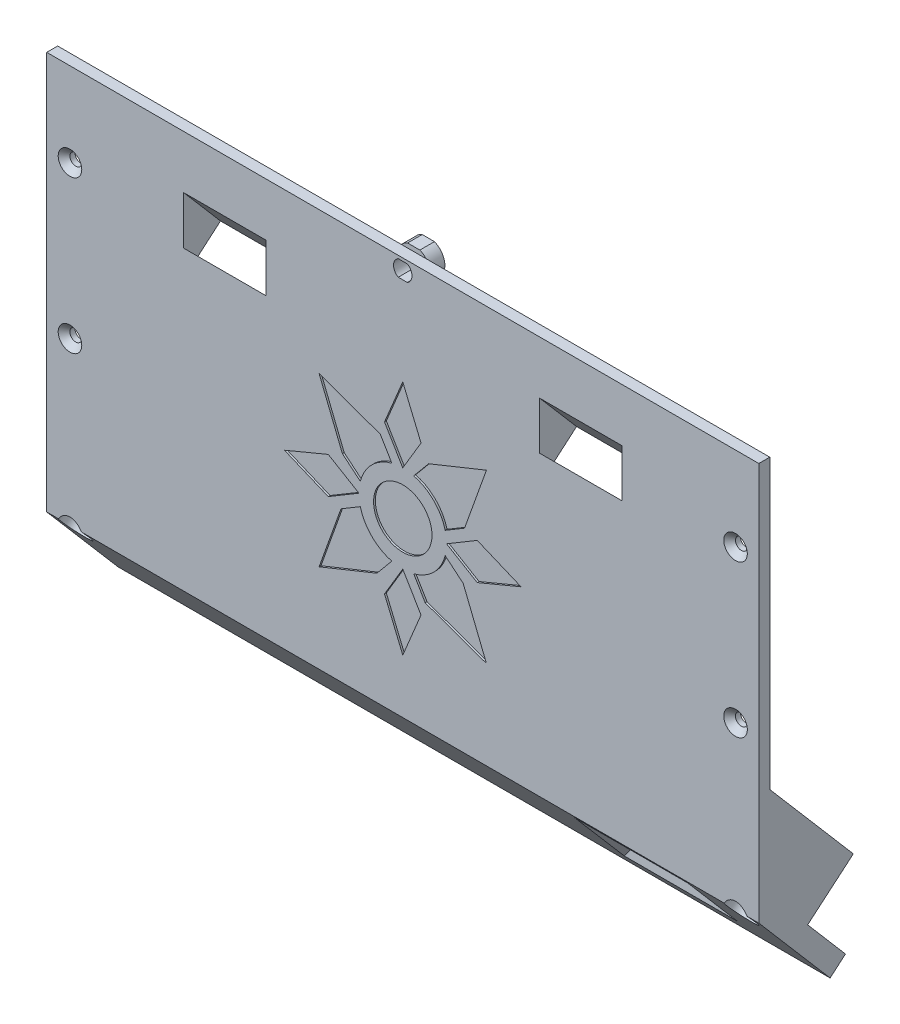
SolidWorks part; units mm, degrees
ref_plane "Alzado" through (0, 0, 0) normal (0, 0, 1) x (1, 0, 0)
ref_plane "Planta" through (0, 0, 0) normal (0, 1, 0) x (1, 0, 0)
ref_plane "Vista lateral" through (0, 0, 0) normal (1, 0, 0) x (0, 0, -1)
sketch "Croquis1" plane through (0, 0, 0) normal (0, 0, 1) x (1, 0, 0)
  line L0 (-97.5, 0) -> (97.5, 0)
  line L1 (97.5, 0) -> (97.5, 38)
  line L2 (97.5, 38) -> (-97.5, 38)
  line L3 (0, 0) -> (0, 28.0598) construction
  line L4 (-97.5, 0) -> (-97.5, 38)
  circle A2 centre (91.125, 15) radius 1.625
  circle A3 centre (-91.125, 15) radius 1.625
  point P13 (0, 38)
  point P14 (0, 0)
  dimension "D1" = 3.25
  dimension "D2" = 15
  dimension "D3" = 97.5
  dimension "D4" = 38
  dimension "D5" = 6.375
extrude "Saliente-Extruir1" add sketch "Croquis1" along normal blind 3
sketch "Croquis8" plane through (0, 0, 0) normal (0, -1, 0) x (1, 0, 0)
  line L1 (-97.5, 3) -> (97.5, 3)
  line L2 (-97.5, 3) -> (-97.5, 0)
  line L3 (-97.5, 0) -> (97.5, 0)
  line L4 (97.5, 3) -> (97.5, 0)
extrude "Saliente-Extruir5" add sketch "Croquis8" along normal blind 5
sketch "Croquis9" plane through (0, 38, 0) normal (0, 1, 0) x (1, 0, 0)
  line L1 (-97.5, 0) -> (97.5, 0)
  line L2 (-97.5, 0) -> (-97.5, -3)
  line L3 (-97.5, -3) -> (97.5, -3)
  line L4 (97.5, 0) -> (97.5, -3)
extrude "Saliente-Extruir6" add sketch "Croquis9" along normal blind 5
sketch "Croquis10" plane through (97.5, 0, 0) normal (1, 0, 0) x (0, 0, -1)
  line L0 (0, 35.3168) -> (11.1006, 22.3656)
  line L1 (1.23, 13.9055) -> (0, 12.8513)
  line L2 (0, 35.3168) -> (0, 12.8513)
  line L3 (0, -5) -> (0, 43) construction
  line L4 (11.1006, 22.3656) -> (1.23, 13.9055)
  line L6 (-3, 18.8408) -> (0, 15.3406) construction
  line L7 (-3, -5) -> (-3, 43) construction
  line L8 (-3, 18.8408) -> (5.5756, 26.191) construction
  dimension "D1" = 5
  dimension "D2" = 6.5
  dimension "D3" = 14.62
  dimension "D4" = 40.6
extrude "Saliente-Extruir7" add sketch "Croquis10" against normal blind 35 from offset 35 offset against normal yes
sketch "Croquis11" plane through (0, 7.4087, 6.35) normal (0, -0.7593, -0.6508) x (1, 0, 0)
  line L3 (60, -13.4833) -> (37.5, -13.4833)
  line L6 (37.5, -13.4833) -> (37.5, -21.9833)
  line L7 (37.5, -21.9833) -> (60, -21.9833)
  line L8 (60, -21.9833) -> (60, -13.4833)
  line L9 (62.5, -8.3633) -> (62.5, -22.9833) construction
  line L10 (27.5, -22.9833) -> (62.5, -22.9833) construction
  dimension "D1" = 8.5
  dimension "D2" = 22.5
  dimension "D3" = 2.5
  dimension "D4" = 1
extrude "Cortar-Extruir4" cut sketch "Croquis11" against normal through all both and the other way through all
sketch "Croquis12" plane through (62.5, 0, 0) normal (1, 0, 0) x (0, 0, -1)
  line L0 (11.1006, 22.3656) -> (0, 12.8513)
  line L1 (0, 12.8513) -> (0, 19.4365)
  line L2 (0, -5) -> (0, 43) construction
  line L3 (0, 19.4365) -> (7.8467, 26.162)
  line L4 (11.1006, 22.3656) -> (0, 35.3168) construction
  line L5 (7.8467, 26.162) -> (11.1006, 22.3656)
  dimension "D1" = 5
extrude "Cortar-Extruir5" cut sketch "Croquis12" against normal up to next
sketch "Croquis13" plane through (0, 11.205, 9.6039) normal (0, -0.7593, -0.6508) x (1, 0, 0)
  line L0 (27.5, -12.6488) -> (27.5, -22.9833) construction
  line L3 (27.5, -22.9833) -> (62.5, -22.9833) construction
  circle A0 centre (33.75, -17.8233) radius 1
  dimension "D1" = 2
  dimension "D3" = 5.16
  dimension "D2" = 6.25
extrude "Cortar-Extruir6" cut sketch "Croquis13" against normal blind 5
sketch "Croquis14" plane through (-97.5, 0, 0) normal (-1, 0, 0) x (0, 0, 1)
  line L0 (0, 19.4365) -> (-7.8467, 26.162)
  line L1 (-7.8467, 26.162) -> (0, 35.3168)
  line L2 (0, 35.3168) -> (0, 19.4365)
extrude "Saliente-Extruir8" add sketch "Croquis14" against normal blind 35 from offset 35 offset against normal yes
sketch "Croquis16" plane through (0, 11.205, 9.6039) normal (0, -0.7593, -0.6508) x (1, 0, 0)
  line L0 (0, 0) -> (0, -29.2293) construction
  line L5 (-37.5, -21.9833) -> (-60, -21.9833)
  line L6 (-60, -13.411) -> (-60, -21.9833)
  line L8 (-37.5, -13.411) -> (-60, -13.411)
  line L9 (60, -21.9833) -> (37.5, -21.9833) construction
  line L10 (-37.5, -13.411) -> (-37.5, -21.9833)
  line L11 (-62.5, -22.9833) -> (-62.5, -12.6488) construction
  dimension "D1" = 22.5
  dimension "D2" = 2.5
extrude "Cortar-Extruir7" cut sketch "Croquis16" against normal through all both and the other way through all
sketch "Croquis17" plane through (0, 11.205, 9.6039) normal (0, -0.7593, -0.6508) x (1, 0, 0)
  line L0 (0, 0) -> (0, -24) construction
  line L1 (-27.5, -22.9833) -> (-62.5, -22.9833) construction
  line L3 (-37.5, -21.9833) -> (-37.5, -13.411) construction
  circle A1 centre (-33.75, -17.8233) radius 1
  dimension "D1" = 5.16
  dimension "D2" = 3.75
extrude "Cortar-Extruir8" cut sketch "Croquis17" against normal blind 5
sketch "Croquis18" plane through (0, 0, 3) normal (0, 0, 1) x (1, 0, 0)
  line L0 (-97.5, 19) -> (97.5, 19) construction
  circle A2 centre (91.125, 23) radius 1.625
  circle A3 centre (-91.125, 23) radius 1.625
extrude "Cortar-Extruir9" cut sketch "Croquis18" against normal blind 10
sketch "Croquis19" plane through (0, 0, 3) normal (0, 0, 1) x (1, 0, 0)
  line L0 (-97.5, 43) -> (-97.5, -5) construction
  line L1 (-97.5, 19) -> (97.5, 19)
  line L2 (-97.5, 19) -> (-97.5, -5)
  line L3 (-97.5, -5) -> (97.5, -5)
  line L4 (97.5, 19) -> (97.5, -5)
extrude "Saliente-Extruir9" add sketch "Croquis19" against normal up to vertex (3 mm away) up to point (-97.5, -5, 0)
sketch "Croquis20" plane through (0, 0, 3) normal (0, 0, 1) x (1, 0, 0)
  line L0 (-97.5, 43) -> (97.5, 43) construction
  line L1 (-97.5, -5) -> (97.5, -5)
  line L2 (-97.5, -5) -> (-97.5, -33.69)
  line L3 (-97.5, -33.69) -> (97.5, -33.69)
  line L4 (97.5, -5) -> (97.5, -33.69)
  dimension "D1" = 76.69
extrude "Saliente-Extruir10" add sketch "Croquis20" against normal up to vertex (3 mm away) up to point (-97.5, -5, 0)
sketch "Croquis22" plane through (0, 0, 3) normal (0, 0, 1) x (1, 0, 0)
  line L0 (-97.5, 43) -> (-97.5, -33.69) construction
  line L1 (-97.5, 43) -> (97.5, 43)
  line L2 (-97.5, 43) -> (-97.5, 51.7993)
  line L3 (-97.5, 51.7993) -> (97.5, 51.7993)
  line L4 (97.5, 43) -> (97.5, 51.7993)
  line L5 (-97.5, 27.545) -> (-86.6825, 27.545)
  line L6 (-97.5, 27.545) -> (-97.5, 18.136)
  line L7 (-97.5, 18.136) -> (-86.6825, 18.136)
  line L8 (-86.6825, 27.545) -> (-86.6825, 18.136)
  line L9 (97.5, -33.69) -> (97.5, 43) construction
  line L10 (86.4429, 27.545) -> (97.5, 27.545)
  line L11 (86.4429, 27.545) -> (86.4429, 18.136)
  line L12 (86.4429, 18.136) -> (97.5, 18.136)
  line L13 (97.5, 27.545) -> (97.5, 18.136)
extrude "Saliente-Extruir11" add sketch "Croquis22" against normal up to vertex (3 mm away) up to point (-97.5, -33.69, 0)
sketch "Croquis23" plane through (0, 0, 3) normal (0, 0, 1) x (1, 0, 0)
  line L1 (-97.5, 51.7993) -> (-97.5, -33.69) construction
  line L2 (97.5, 51.7993) -> (-97.5, 51.7993) construction
  line L3 (0, -1.1555) -> (0, 35.7449) construction
  circle A0 centre (-91.125, 28.7993) radius 1.625
  circle A1 centre (-91.125, -12.8907) radius 1.625
  circle A2 centre (91.125, -12.8907) radius 1.625
  circle A3 centre (91.125, 28.7993) radius 1.625
  dimension "D1" = 6.375
  dimension "D2" = 23
  dimension "D3" = 41.69
  dimension "D4" = 3.25
extrude "Cortar-Extruir10" cut sketch "Croquis23" against normal blind 10
sketch "Croquis25" plane through (-97.5, 0, 0) normal (-1, 0, 0) x (0, 0, 1)
  line L0 (0, 51.7993) -> (0, -33.69) construction
  line L1 (0, -27.2007) -> (6.0483, -27.2007)
  line L2 (0, -27.2007) -> (0, -41.7759)
  line L3 (0, -41.7759) -> (6.0483, -41.7759)
  line L4 (6.0483, -27.2007) -> (6.0483, -41.7759)
  line L5 (0, 51.7993) -> (3, 51.7993) construction
  dimension "D1" = 79
extrude "Cortar-Extruir11" cut sketch "Croquis25" against normal through all both and the other way through all
sketch "Croquis29" plane through (97.5, 0, 0) normal (1, 0, 0) x (0, 0, -1)
  line L0 (-3, -27.2007) -> (21.0476, -55.2576)
  line L1 (-3, -27.2007) -> (-1.1795, -25.6404)
  line L2 (21.0476, -55.2576) -> (22.8681, -53.6972)
  line L3 (-1.1795, -25.6404) -> (22.8681, -53.6972)
  line L4 (7.8467, 26.162) -> (0, 35.3168) construction
  dimension "D1" = 35
extrude "Saliente-Extruir15" add sketch "Croquis29" against normal blind 12.75
sketch "Croquis30" plane through (-97.5, 0, 0) normal (-1, 0, 0) x (0, 0, 1)
  line L0 (0, -27.2007) -> (3, -27.2007)
  line L1 (3, -27.2007) -> (-21.0476, -55.2576)
  line L2 (-21.0476, -55.2576) -> (-22.8681, -53.6972)
  line L3 (-22.8681, -53.6972) -> (0, -27.2007)
extrude "Saliente-Extruir16" add sketch "Croquis30" against normal blind 12.75
sketch "Croquis27" plane through (97.5, 0, 0) normal (1, 0, 0) x (0, 0, -1)
  line L1 (-3, -27.2007) -> (0, -27.2007)
  line L2 (-3, -27.2007) -> (-3, -57.2007)
  line L3 (-3, -57.2007) -> (0, -57.2007)
  line L4 (0, -27.2007) -> (0, -57.2007)
  dimension "D1" = 30
extrude "Saliente-Extruir13" add sketch "Croquis27" against normal blind 195
sketch "Croquis28" plane through (97.5, 0, 0) normal (1, 0, 0) x (0, 0, -1)
  line L0 (0, -52.2007) -> (20.7233, -76.379)
  line L1 (0, -52.2007) -> (-3, -54.772)
  line L2 (20.7233, -76.379) -> (16.2045, -80.252)
  line L4 (0, -57.2007) -> (0, -30.7009) construction
  line L5 (7.8467, 26.162) -> (0, 35.3168) construction
  line L6 (-3, -57.2007) -> (0, -57.2007) construction
  line L7 (-3, -57.2007) -> (16.5232, -79.9789)
  line L8 (-3, -54.772) -> (-3, -57.2007)
  line L9 (-3, -57.2007) -> (-3, 51.7993) construction
  line M6 (-3, 51.7993) -> (-3, -57.2007)
  line M7 (-3, -57.2007) -> (0, -57.2007)
  line M8 (0, -57.2007) -> (0, -30.7009)
  dimension "D1" = 5
  dimension "D2" = 30
extrude "Saliente-Extruir14" add sketch "Croquis28" against normal blind 195 contours L7 L2 L0 M7 M8 | L1 M8 M6 M7 region at (97.5, -55.2694, 1.3269) region at (97.5, -66.9176, -9.0188)
sketch "Croquis31" plane through (0, -13.002, 15.1697) normal (0, -0.6508, 0.7593) x (1, 0, 0)
  line L1 (0, 0) -> (0, -106.5046) construction
  line L2 (97.5, -20.5129) -> (84.75, -20.5129) construction
  circle A0 centre (91.125, -43.9629) radius 1.625
  circle A1 centre (-91.125, -43.9629) radius 1.625
  dimension "D1" = 3.25
  dimension "D2" = 23.45
extrude "Cortar-Extruir12" cut sketch "Croquis31" against normal through all both and the other way through all
sketch "Croquis32" plane through (97.5, 0, 0) normal (1, 0, 0) x (0, 0, -1)
  line L0 (0, -30.7009) -> (21.0476, -55.2576)
  line L1 (21.0476, -55.2576) -> (10.3616, -64.2899)
  line L2 (0, -52.2007) -> (20.7233, -76.379) construction
  line L3 (10.3616, -64.2899) -> (0, -52.2007)
  line L4 (0, -52.2007) -> (0, -30.7009)
extrude "Saliente-Extruir17" add sketch "Croquis32" against normal blind 12.75
sketch "Croquis33" plane through (-97.5, 0, 0) normal (-1, 0, 0) x (0, 0, 1)
  line L0 (0, -30.7009) -> (0, -52.2007)
  line L1 (0, -52.2007) -> (-10.3616, -64.2899)
  line L2 (-10.3616, -64.2899) -> (-21.0476, -55.2576)
  line L3 (-21.0476, -55.2576) -> (0, -30.7009)
extrude "Saliente-Extruir18" add sketch "Croquis33" against normal blind 12.75
sketch "Croquis39" plane through (0, -11.4417, 13.3493) normal (0, 0.6508, -0.7593) x (-1, 0, 0)
  circle A0 centre (91.125, -43.9629) radius 1.625
  circle A1 centre (-91.125, -43.9629) radius 1.625
extrude "Cortar-Extruir15" cut sketch "Croquis39" against normal through all both and the other way through all
sketch "Croquis40" plane through (0, -11.4417, 13.3493) normal (0, 0.6508, -0.7593) x (-1, 0, 0)
  circle A0 centre (-91.125, -43.9629) radius 4
  circle A1 centre (91.125, -43.9629) radius 4
  dimension "D1" = 8
  dimension "D2" = 8
extrude "Cortar-Extruir16" cut sketch "Croquis40" against normal through all from offset 4 offset against normal yes
sketch "Croquis43" plane through (0, -54.2716, -46.5164) normal (0, -0.7593, -0.6508) x (1, 0, 0)
  line L0 (-97.5, 33.9709) -> (97.5, 33.9709) construction
  line L1 (-10, 33.9709) -> (10, 33.9709)
  line L2 (-10, 33.9709) -> (-10, 23.9709)
  line L3 (-10, 23.9709) -> (-3.75, 23.9709)
  line L4 (10, 33.9709) -> (10, 23.9709)
  line L5 (-3.75, 28.9709) -> (-3.75, 23.9709)
  line L7 (3.75, 23.9709) -> (3.75, 28.9709)
  line L8 (3.75, 23.9709) -> (10, 23.9709)
  arc A0 (3.75, 28.9709) -> (-3.75, 28.9709) centre (0, 28.9709) ccw
  dimension "D4" = 7.5
  dimension "D5" = 5
  dimension "D1" = 10
  dimension "D2" = 20
  dimension "D3" = 10
extrude "Saliente-Extruir19" add sketch "Croquis43" against normal blind 4 from offset 15 offset against normal yes
chamfer "Chaflán1" distance 10 angle 45 2 edges at (-10, -63.4714, -9.6601) (10, -63.4714, -9.6601)
sketch "Croquis44" plane through (-97.5, 0, 0) normal (-1, 0, 0) x (0, 0, 1)
  line L5 (-28.6278, -60.4172) -> (-16.184, -71.0829)
  line L6 (-10.3616, -64.2899) -> (-20.7233, -76.379) construction
  line L7 (-16.184, -71.0829) -> (-10.3616, -64.2899)
  line L8 (-10.3616, -64.2899) -> (-22.8681, -53.6972)
  line L9 (-22.8681, -53.6972) -> (-28.6278, -60.4172)
  dimension "D1" = 43.9904
extrude "Saliente-Extruir20" add sketch "Croquis44" against normal blind 3
sketch "Croquis47" plane through (0, -25.7073, 29.9932) normal (0, -0.6508, 0.7593) x (1, 0, 0)
  line L0 (-87.9901, -41.4785) -> (87.9901, -41.4785) construction
  line L1 (48.7328, -46.4785) -> (73.7328, -46.4785)
  line L2 (48.7328, -46.4785) -> (48.7328, -61.4785)
  line L3 (48.7328, -61.4785) -> (73.7328, -61.4785)
  line L4 (73.7328, -46.4785) -> (73.7328, -61.4785)
  dimension "D1" = 15
  dimension "D2" = 25
  dimension "D3" = 5
extrude "Cortar-Extruir17" cut sketch "Croquis47" against normal up to next
sketch "Croquis48" plane through (0, 0, 3) normal (0, 0, 1) x (1, 0, 0)
  line L0 (97.5, 51.7993) -> (-97.5, 51.7993) construction
  line L2 (-1.2392, 50.9993) -> (1.2392, 50.9993)
  line L4 (1.2392, 46.5993) -> (-1.2392, 46.5993)
  arc A0 (-2.2, 47.5601) -> (-1.2392, 46.5993) centre (0, 48.7993) ccw construction
  arc A2 (-2.2, 47.5601) -> (-1.2392, 46.5993) centre (0, 48.7993) ccw
  arc A3 (-1.2392, 50.9993) -> (-1.2392, 46.5993) centre (0, 48.7993) ccw
  arc A4 (1.2392, 46.5993) -> (1.2392, 50.9993) centre (0, 48.7993) ccw
  dimension "D2" = 5.05
  dimension "D1" = 3
  dimension "D3" = 2.2
  dimension "D4" = 2.2
extrude "Cortar-Extruir18" cut sketch "Croquis48" against normal up to next contours L4 A4 L2 A3 A2 region at (0, 48.7993, 3)
sketch "Croquis49" plane through (0, 0, 3) normal (0, 0, 1) x (1, 0, 0)
  line L2 (0, -10) -> (0, 0) construction
  line L20 (0, 2) -> (-5, 10.3961)
  line L21 (-5, 10.3961) -> (0, 22.3961)
  line L36 (5, 10.3961) -> (0, 22.3961)
  line L37 (0, 2) -> (5, 10.3961)
  line L50 (-6.1541, 6.9153) -> (-3, 1.619)
  line L51 (-16.5376, -2.8931) -> (-11.619, -7)
  line L52 (-11.619, -7) -> (-3, 1.619) construction
  line L53 (0, -10) -> (-22.9075, 12.9075) construction
  line L54 (-16.5376, -2.8931) -> (-22.9075, 12.9075)
  line L55 (-22.9075, 12.9075) -> (-6.1541, 6.9153)
  line L56 (12, -10) -> (20.3961, -15)
  line L57 (12, -10) -> (20.3961, -5)
  line L58 (20.3961, -5) -> (32.3961, -10)
  line L59 (20.3961, -15) -> (32.3961, -10)
  line L60 (0, -22) -> (-5, -30.3961)
  line L61 (0, -22) -> (5, -30.3961)
  line L62 (5, -30.3961) -> (0, -42.3961)
  line L63 (-5, -30.3961) -> (0, -42.3961)
  line L64 (-12, -10) -> (-20.3961, -5)
  line L65 (-12, -10) -> (-20.3961, -15)
  line L66 (-20.3961, -15) -> (-32.3961, -10)
  line L67 (-20.3961, -5) -> (-32.3961, -10)
  line L68 (0, -10) -> (0, 2) construction
  line L69 (7.1069, 6.5376) -> (3, 1.619)
  line L70 (7.1069, 6.5376) -> (22.9075, 12.9075)
  line L71 (22.9075, 12.9075) -> (16.9153, -3.8459)
  line L72 (16.9153, -3.8459) -> (11.619, -7)
  line L73 (16.5376, -17.1069) -> (11.619, -13)
  line L74 (16.5376, -17.1069) -> (22.9075, -32.9075)
  line L75 (22.9075, -32.9075) -> (6.1541, -26.9153)
  line L76 (6.1541, -26.9153) -> (3, -21.619)
  line L77 (-7.1069, -26.5376) -> (-3, -21.619)
  line L78 (-7.1069, -26.5376) -> (-22.9075, -32.9075)
  line L79 (-22.9075, -32.9075) -> (-16.9153, -16.1541)
  line L80 (-16.9153, -16.1541) -> (-11.619, -13)
  line L81 (0, -10) -> (-3, 1.619) construction
  circle A8 centre (0, -10) radius 8
  circle A9 centre (0, -10) radius 18 construction
  circle A10 centre (0, -10) radius 21 construction
  circle A11 centre (0, -10) radius 12
  circle A12 centre (0, -10) radius 32.3961 construction
  dimension "D1" = 16
  dimension "D2" = 4
  dimension "D3" = 6
  dimension "D4" = 3
  dimension "D10" = 12
  dimension "D5" = 10
  dimension "D6" = 12
  dimension "D7" = 5
  dimension "D9" = 3
  dimension "D11" = 3
  dimension "D12" = 11.619
  dimension "D13" = 4
  dimension "D14" = 12
  dimension "D8" = 4
extrude "Cortar-Extruir19" cut sketch "Croquis49" against normal blind 0.5 contours A11 L50 L55 L54 L51 | L20 L37 L36 L21 | A11 L72 L71 L70 L69 | L56 L59 L58 L57 | A11 L76 L75 L74 L73 | A8 | L60 L63 L62 L61 | A11 L80 L79 L78 L77 | L64 L67 L66 L65
chamfer "Chaflán2" distance 3 angle 45 4 edges at (73.7328, -66.6916, -5.1347) (61.2328, -60.9971, -0.2539) (48.7328, -66.6916, -5.1347) (61.2328, -72.3862, -10.0155)
sketch "Croquis51" plane through (0, 0, 0) normal (0, 0, -1) x (-1, 0, 0)
  line L10 (-1.6839, 44.5993) -> (1.6839, 44.5993)
  line L11 (1.6839, 52.9993) -> (-1.6839, 52.9993)
  line L12 (-1.6839, 44.5993) -> (1.6839, 44.5993)
  line L13 (1.6839, 52.9993) -> (-1.6839, 52.9993)
  line L16 (-1.2392, 46.5993) -> (1.2392, 46.5993)
  line L17 (1.2392, 50.9993) -> (-1.2392, 50.9993)
  line L18 (-1.2392, 46.5993) -> (1.2392, 46.5993)
  line L19 (1.2392, 50.9993) -> (-1.2392, 50.9993)
  arc A10 (-1.6839, 52.9993) -> (-1.6839, 44.5993) centre (0, 48.7993) ccw
  arc A11 (1.6839, 44.5993) -> (1.6839, 52.9993) centre (0, 48.7993) ccw
  arc A12 (-1.6839, 52.9993) -> (-1.6839, 44.5993) centre (0, 48.7993) ccw
  arc A13 (1.6839, 44.5993) -> (1.6839, 52.9993) centre (0, 48.7993) ccw
  arc A16 (1.2392, 46.5993) -> (1.2392, 50.9993) centre (0, 48.7993) ccw
  arc A17 (-1.2392, 50.9993) -> (-1.2392, 46.5993) centre (0, 48.7993) ccw
  arc A18 (1.2392, 46.5993) -> (1.2392, 50.9993) centre (0, 48.7993) ccw
  arc A19 (-1.2392, 50.9993) -> (-1.2392, 46.5993) centre (0, 48.7993) ccw
  dimension "D1" = 2
  dimension "D2" = 0
extrude "Saliente-Extruir22" add sketch "Croquis51" along normal blind 4
chamfer "Chaflán3" distance 1.6 angle 45 4 edges at (-89.5, -12.8907, 3) (-89.5, 28.7993, 3) (89.5, -12.8907, 3) (89.5, 28.7993, 3)
